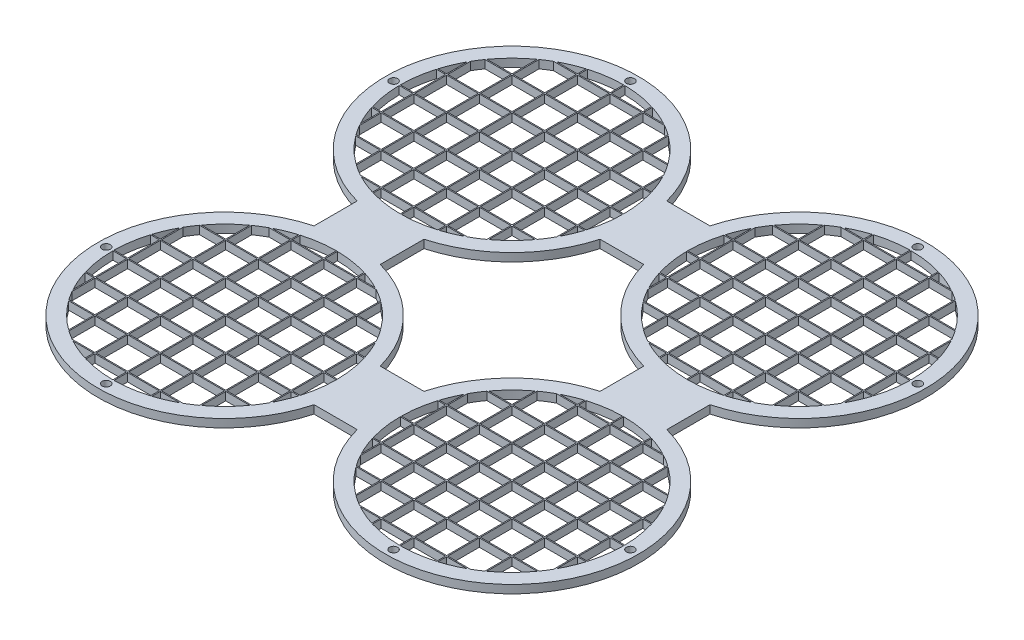
SolidWorks part; units mm, degrees
ref_plane "Front Plane" through (0, 0, 0) normal (0, 0, 1) x (1, 0, 0)
ref_plane "Top Plane" through (0, 0, 0) normal (0, 1, 0) x (1, 0, 0)
ref_plane "Right Plane" through (0, 0, 0) normal (1, 0, 0) x (0, 0, -1)
sketch "Sketch2" plane through (0, 0, 0) normal (0, 1, 0) x (1, 0, 0)
  circle A1 centre (0, 0) radius 41
  circle A2 centre (0, 0) radius 46
  point P208 (0, 0)
extrude "Boss-Extrude2" add sketch "Sketch2" along normal blind 3
sketch "Sketch4" plane through (0, 3, 0) normal (0, 1, 0) x (1, 0, 0)
  line L0 (0, 46) -> (0, -46)
  line L1 (12, 44.4072) -> (12, -44.4072)
  line L2 (24, 39.2428) -> (24, -39.2428)
  line L3 (36, 28.6356) -> (36, -28.6356)
  line L4 (-12, 44.4072) -> (-12, -44.4072)
  line L5 (-24, 39.2428) -> (-24, -39.2428)
  line L6 (-36, 28.6356) -> (-36, -28.6356)
  line L7 (-46, 0) -> (46, 0)
  line L8 (-44.4072, -12) -> (44.4072, -12)
  line L9 (-39.2428, -24) -> (39.2428, -24)
  line L10 (-28.6356, -36) -> (28.6356, -36)
  line L11 (-44.4072, 12) -> (44.4072, 12)
  line L12 (-39.2428, 24) -> (39.2428, 24)
  line L13 (-28.6356, 36) -> (28.6356, 36)
  circle A1 centre (0, 0) radius 46 construction
  circle A2 centre (0, 0) radius 46
  dimension "D1" = 4
  dimension "D2" = 4
extrude "Extrude-Thin5" add sketch "Sketch4" against normal blind 3 thin thin type one direction wall 0.4
sketch "Sketch5" plane through (0, 0, 0) normal (0, -1, 0) x (1, 0, 0)
  circle A0 centre (0, -43.4524) radius 1.5
  circle A3 centre (43.4524, 0) radius 1.5
  circle A4 centre (0, 43.4524) radius 1.5 [skipped]
  circle A5 centre (-43.4524, 0) radius 1.5 [skipped]
  point P11 (0, 0)
  dimension "D1" = 4
extrude "Cut-Extrude1" cut sketch "Sketch5" against normal blind 3
ref_plane "Plane1" through (-52.73, 0, 0) normal (1, 0, 0) x (0, 0, -1)
mirror "Mirror6" about plane through (-52.73, 0, 0) normal (1, 0, 0) of bodies 145
sketch "Sketch6" plane through (0, 0, 0) normal (0, -1, 0) x (1, 0, 0)
  line L0 (-66.2554, -12) -> (-69.06, -12) construction
  line L1 (-63.8736, 12.4) -> (-41.5573, 12.4)
  line L2 (-63.8736, 12.4) -> (-63.8736, -12)
  line L3 (-63.8736, -12) -> (-41.5573, -12)
  line L4 (-41.5573, 12.4) -> (-41.5573, -12)
  line L5 (-66.3801, 12.4) -> (-69.06, 12.4) construction
extrude "Boss-Extrude3" add sketch "Sketch6" against normal up to surface (3 mm away)
ref_plane "Plane2" through (0, 0, 52.73) normal (0, 0, 1) x (1, 0, 0)
mirror "Mirror8" about plane through (0, 0, 52.73) normal (0, 0, 1) of bodies 165
sketch "Sketch7" plane through (0, 3, 0) normal (0, 1, 0) x (1, 0, 0)
  line L0 (-93.06, -36.4) -> (-93.06, -39.0799) construction
  line L1 (-117.46, -41.6172) -> (-93.06, -41.6172)
  line L2 (-117.46, -41.6172) -> (-117.46, -64.0066)
  line L3 (-117.46, -64.0066) -> (-93.06, -64.0066)
  line L4 (-93.06, -41.6172) -> (-93.06, -64.0066)
  line L5 (-117.46, -36.4) -> (-117.46, -39.2046) construction
extrude "Boss-Extrude4" add sketch "Sketch7" against normal up to surface (3 mm away) up to face at (-52.73, 0, -0.0036)
sketch "Sketch8" plane through (0, 3, 0) normal (0, 1, 0) x (1, 0, 0)
  line L0 (-12.4, -36.4) -> (-12.4, -39.0799) construction
  line L1 (-12.4, -41.7611) -> (12, -41.7611)
  line L2 (-12.4, -41.7611) -> (-12.4, -64.1646)
  line L3 (-12.4, -64.1646) -> (12, -64.1646)
  line L4 (12, -41.7611) -> (12, -64.1646)
  line L5 (12, -36.4) -> (12, -39.2046) construction
extrude "Boss-Extrude5" add sketch "Sketch8" against normal up to surface (3 mm away) up to face at (-62.5401, 0, 52.73)
